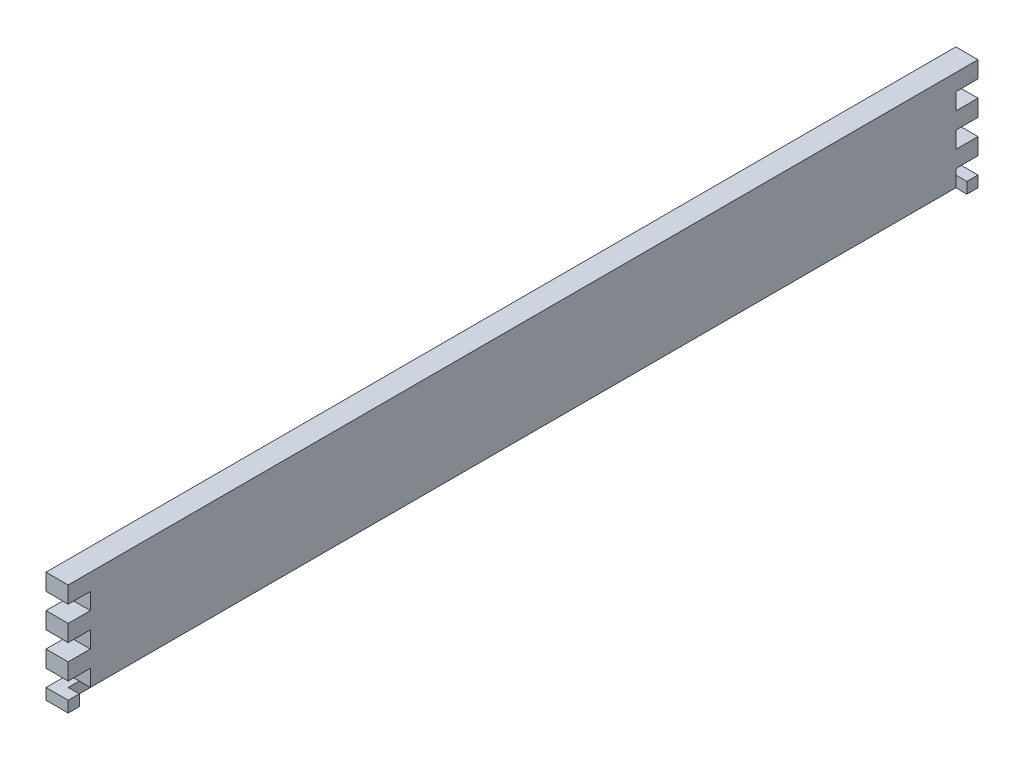
SolidWorks part; units mm, degrees
material "Сосна"
ref_plane "Спереди" through (0, 0, 0) normal (0, 0, 1) x (1, 0, 0)
ref_plane "Сверху" through (0, 0, 0) normal (0, 1, 0) x (1, 0, 0)
ref_plane "Справа" through (0, 0, 0) normal (1, 0, 0) x (0, 0, -1)
sketch "Эскиз1" plane through (0, 0, 0) normal (0, 0, 1) x (1, 0, 0)
  line L0 (0, 0) -> (0, 100)
  line L3 (0, 100) -> (20, 100)
  line L4 (20, 100) -> (20, 10)
  line L5 (20, 10) -> (10, 10)
  line L6 (10, 10) -> (10, 0)
  line L7 (10, 0) -> (0, 0)
  dimension "D1" = 100
  dimension "D2" = 20
  dimension "D3" = 10
  dimension "D4" = 10
extrude "Бобышка-Вытянуть1" add sketch "Эскиз1" along normal blind 820
sketch "Эскиз3" plane through (10, 0, 0) normal (1, 0, 0) x (0, 0, -1)
  line L0 (-820, 10) -> (0, 10) construction
  line L1 (-820, 0) -> (-810, 0)
  line L2 (-820, 0) -> (-820, 10)
  line L3 (-820, 10) -> (-810, 10)
  line L4 (-810, 0) -> (-810, 10)
  line L5 (-410, 0) -> (-410, 110.6456) construction
  line L7 (-820, 0) -> (0, 0) construction
  line L8 (-10, 0) -> (-10, 10)
  line L9 (0, 10) -> (-10, 10)
  line L10 (0, 0) -> (0, 10)
  line L11 (0, 0) -> (-10, 0)
  dimension "D1" = 10
extrude "Бобышка-Вытянуть2" add sketch "Эскиз3" along normal blind 10
sketch "Эскиз4" plane through (0, 0, 0) normal (-1, 0, 0) x (0, 0, 1)
  line L0 (820, 100) -> (820, 0) construction
  line L1 (820, 85) -> (800, 85)
  line L2 (820, 85) -> (820, 70)
  line L3 (820, 70) -> (800, 70)
  line L4 (800, 85) -> (800, 70)
  line L5 (820, 100) -> (0, 100) construction
  dimension "D1" = 20
  dimension "D2" = 15
  dimension "D3" = 15
extrude "Вырез-Вытянуть1" cut sketch "Эскиз4" against normal through all
pattern_linear "Линейный массив1" count 1 spacing 10 along (0, 0, -1) count 3 spacing 30 along (0, -1, 0) of "Вырез-Вытянуть1"
pattern_linear "Линейный массив2" count 2 spacing 800 along (0, 0, -1) of "Линейный массив1"
